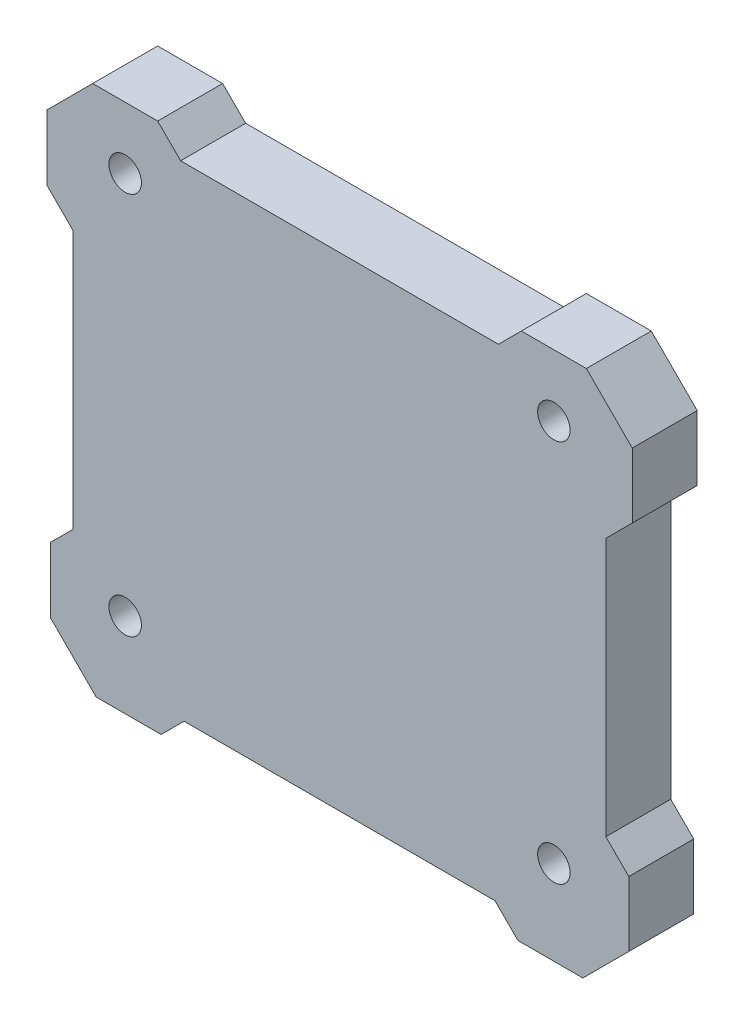
SolidWorks part; units mm, degrees
ref_plane "Alzado" through (0, 0, 0) normal (0, 0, 1) x (1, 0, 0)
ref_plane "Planta" through (0, 0, 0) normal (0, 1, 0) x (1, 0, 0)
ref_plane "Vista lateral" through (0, 0, 0) normal (1, 0, 0) x (0, 0, -1)
sketch "Croquis1" plane through (0, 0, 0) normal (0, 0, 1) x (1, 0, 0)
  line L0 (0, 0) -> (0, 36.5) construction
  line L5 (33, 29.5) -> (-33, 29.5)
  line L10 (33, 29.5) -> (33, -29.5)
  line L11 (33, -29.5) -> (-33, -29.5)
  line L12 (-33, 29.5) -> (-33, -29.5)
  line L13 (33, 29.5) -> (-33, -29.5) construction
  line L14 (33, -29.5) -> (-33, 29.5) construction
  line L15 (-41, 39) -> (41, 39)
  line L16 (-41, 39) -> (-41, -39)
  line L17 (-41, -39) -> (41, -39)
  line L18 (41, 39) -> (41, -39)
  line L19 (-41, 39) -> (41, -39) construction
  line L20 (-41, -39) -> (41, 39) construction
  circle A0 centre (-33, 29.5) radius 2.5
  circle A1 centre (33, 29.5) radius 2.5
  circle A2 centre (33, -29.5) radius 2.5
  circle A3 centre (-33, -29.5) radius 2.5
  point P0 (0, 0)
  point P5 (0, 0)
  dimension "D5" = 36.5
  dimension "D1" = 66
  dimension "D2" = 59
  dimension "D3" = 78
  dimension "D4" = 82
extrude "Saliente-Extruir5" add sketch "Croquis1" along normal blind 10 contours L15 | A3 L11 A2 L10 A1 L5 A0 L12 | L18 L15 L16 L17 A3 L12 A0 L5 A1 L10 A2 L11 region at (0, 0, 0) region at (0, 37.8683, 0)
sketch "Croquis6" plane through (0, 0, 10) normal (0, 0, 1) x (1, 0, 0)
  line L2 (-41, 39) -> (0, 39) construction
  line L3 (-38, 39) -> (38, 39)
  line L4 (-41, 39) -> (41, 39) construction
  line L5 (38, 39) -> (45.0711, 31.9289)
  line L6 (38, 39) -> (38, -39) construction
  line L7 (-41, -39) -> (41, -39) construction
  line L8 (45.0711, 31.9289) -> (45.0711, 21.9289)
  line L9 (45.0711, 21.9289) -> (41, 17.8579)
  line L10 (41, -39) -> (44.5355, -35.4645)
  line L11 (41, 39) -> (41, -39) construction
  line L12 (44.5355, -35.4645) -> (44.5355, -25.4645)
  line L13 (45.0711, 21.9289) -> (41, 21.9289) construction
  line L16 (44.5355, -25.4645) -> (41, -21.9289)
  line L17 (44.5355, -35.4645) -> (37.4645, -42.5355)
  line L18 (37.4645, -42.5355) -> (27.4645, -42.5355)
  line L19 (27.4645, -42.5355) -> (23.9289, -39)
  line L20 (-45.0711, 21.9289) -> (-41, 21.9289) construction
  line L21 (-38, 39) -> (-38, -39) construction
  line L22 (-27.4645, -42.5355) -> (-23.9289, -39)
  line L23 (-37.4645, -42.5355) -> (-27.4645, -42.5355)
  line L24 (-44.5355, -35.4645) -> (-37.4645, -42.5355)
  line L25 (-44.5355, -25.4645) -> (-41, -21.9289)
  line L27 (-44.5355, -35.4645) -> (-44.5355, -25.4645)
  line L28 (-41, -39) -> (-44.5355, -35.4645)
  line L29 (-45.0711, 21.9289) -> (-41, 17.8579)
  line L30 (-45.0711, 31.9289) -> (-45.0711, 21.9289)
  line L31 (-38, 39) -> (-45.0711, 31.9289)
  line M22 (41, 39) -> (-41, 39)
  line M23 (-41, 39) -> (-41, -39)
  line M24 (-41, -39) -> (41, -39)
  line M25 (41, -39) -> (41, 39)
  dimension "D2" = 10
  dimension "D3" = 10
  dimension "D4" = 45
  dimension "D5" = 45
  dimension "D8" = 45
  dimension "D9" = 45
  dimension "D10" = 10
  dimension "D11" = 45
extrude "Saliente-Extruir7" add sketch "Croquis6" against normal through all contours L31 L30 L29 M23 | M22 | L3 | L9 L8 L5 M25 | L12 L16 L10 M25 | L19 L18 L17 M24 | L27 L24 L25 M23 | L24 L23 L22 M24 region at (-42.8392, 26.9289, 10) region at (42.8392, 26.9289, 10) region at (-42.6139, -30.4645, 10) region at (42.6139, -30.4645, 10) region at (-32.4645, -40.6139, 10) region at (32.4645, -40.6139, 10)
sketch "Croquis7" plane through (0, 0, 10) normal (0, 0, 1) x (1, 0, 0)
  line L0 (-45.0711, 31.9289) -> (-38, 39)
  line L1 (-41, 39) -> (41, 39) construction
  line L2 (-38, 39) -> (-28, 39)
  line L3 (-28, 39) -> (-24.4645, 35.4645)
  line L4 (24.4645, 35.4645) -> (-24.4645, 35.4645)
  line L5 (45.0711, 31.9289) -> (38, 39)
  line L6 (38, 39) -> (28, 39)
  line L7 (28, 39) -> (24.4645, 35.4645)
  line L8 (41, 36) -> (41, 39)
  line L9 (41, 39) -> (-41, 39)
  line L10 (-41, 39) -> (-41, 36)
  line L11 (-41, 39) -> (-41, 36) construction
extrude "Cortar-Extruir-Lámina1" cut sketch "Croquis7" against normal through all thin thin type one direction wall 10
